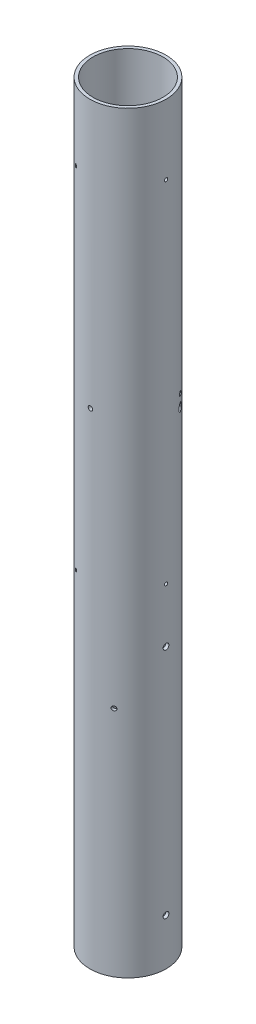
SolidWorks part; units mm, degrees
material "75 Degrees Custom Wound Fiberglass"
ref_plane "Front Plane" through (0, 0, 0) normal (0, 0, 1) x (1, 0, 0)
ref_plane "Top Plane" through (0, 0, 0) normal (0, 1, 0) x (1, 0, 0)
ref_plane "Right Plane" through (0, 0, 0) normal (1, 0, 0) x (0, 0, -1)
sketch "Sketch1" plane through (0, 0, 0) normal (0, 1, 0) x (1, 0, 0)
  circle A0 centre (0, 0) radius 38.227
  circle A1 centre (0, 0) radius 41.656
  dimension "D1" = 76.454
  dimension "D2" = 83.312
extrude "Boss-Extrude1" add sketch "Sketch1" along normal blind 822.5282
ref_axis "Axis1" through (0, -40.64, 0) along (0, 1, 0)
ref_plane "Plane1" through (-20.828, 0, 36.0752) normal (-0.5, 0, 0.866) x (0, -1, 0)
sketch "Sketch2" plane through (-20.828, 0, 36.0752) normal (-0.5, 0, 0.866) x (0, -1, 0)
  line L0 (40.64, 0) -> (-853.44, 0) construction
  line L1 (-822.5282, 38.227) -> (-822.5282, -38.227) construction
  line L2 (-822.5282, 38.227) -> (-822.5282, -38.227) construction
  circle A0 centre (-746.3282, 0) radius 1.778
  dimension "D1" = 76.2
  dimension "D2" = 3.556
extrude "S1A_Coupler" cut sketch "Sketch2" against normal up to next
pattern_circular "S1A_Coupler_Pattern" count 3 over 360 about axis through (0, -40.64, 0) along (0, 1, 0) of "S1A_Coupler"
ref_plane "Plane2" through (41.656, 0, 0) normal (1, 0, 0) x (0, 0, -1)
sketch "Sketch3" plane through (41.656, 0, 0) normal (1, 0, 0) x (0, 0, -1)
  line L0 (0, -40.64) -> (0, 853.44) construction
  circle A0 centre (0, 50.8) radius 3.175
  circle A1 centre (0, 304.8) radius 3.175
  dimension "D1" = 6.35
  dimension "D2" = 6.35
  dimension "D3" = 50.8
  dimension "D4" = 254
extrude "S1A_Rail_Guide" cut sketch "Sketch3" against normal up to next
ref_plane "Plane3" through (0, 530.4282, 0) normal (0, 1, 0) x (1, 0, 0)
ref_axis "Axis2" through (-19.4855, 746.3282, 33.7499) along (-0.5, 0, 0.866)
ref_plane "Plane4" through (-36.366, 0, -20.3159) normal (-0.873, 0, -0.4877) x (0, -1, 0)
sketch "Sketch4" plane through (-36.366, 0, -20.3159) normal (-0.873, 0, -0.4877) x (0, -1, 0)
  line L0 (-530.4282, 43.5864) -> (-530.4282, -43.5864) construction
  line L1 (40.64, 0) -> (-853.44, 0) construction
  circle A0 centre (-530.4282, 0) radius 2.3812
  dimension "D1" = 4.7625
extrude "S1A_Pressure" cut sketch "Sketch4" against normal up to next
pattern_circular "S1A_Pressure_Pattern" count 3 over 360 about axis through (0, -40.64, 0) along (0, 1, 0) of "S1A_Pressure"
ref_plane "Plane5" through (0, 511.3782, 0) normal (0, 1, 0) x (1, 0, 0)
ref_plane "Plane6" through (35.7771, 0, -21.3359) normal (0.8589, 0, -0.5122) x (0, -1, 0)
sketch "Sketch6" plane through (35.7771, 0, -21.3359) normal (0.8589, 0, -0.5122) x (0, -1, 0)
  line L0 (-518.9982, 0) -> (-516.4582, 0) construction
  line L1 (-518.9982, 3.175) -> (-516.4582, 3.175)
  line L2 (-518.9982, -3.175) -> (-516.4582, -3.175)
  line L3 (-822.5282, 0) -> (0, 0) construction
  line L4 (-822.5282, 41.656) -> (-822.5282, -41.656) construction
  arc A0 (-518.9982, 3.175) -> (-518.9982, -3.175) centre (-518.9982, 0) ccw
  arc A1 (-516.4582, -3.175) -> (-516.4582, 3.175) centre (-516.4582, 0) ccw
  point P1 (-517.7282, 0)
  dimension "D1" = 2.54
  dimension "D2" = 3.175
  dimension "D3" = 304.8
extrude "Switch_Slot" cut sketch "Sketch6" against normal up to next
ref_plane "Plane7" through (0, 254, 0) normal (0, 1, 0) x (1, 0, 0)
ref_plane "Plane8" through (20.828, 0, 36.0752) normal (0.5, 0, 0.866) x (0, -1, 0)
sketch "Sketch7" plane through (20.828, 0, 36.0752) normal (0.5, 0, 0.866) x (0, -1, 0)
  line L0 (-254, 43.5864) -> (-254, -43.5864) construction
  circle A0 centre (-254, 0) radius 2.3813
  dimension "D1" = 4.7625
extrude "S1A_Pressure_2" cut sketch "Sketch7" against normal up to next
pattern_circular "S1A_Pressure_2_Pattern" count 3 over 360 about axis through (0, -40.64, 0) along (0, 1, 0) of "S1A_Pressure_2"
sketch "Sketch8" plane through (-20.828, 0, 36.0752) normal (-0.5, 0, 0.866) x (0, -1, 0)
  circle A0 centre (-364.1217, 0) radius 1.7859
  dimension "D1" = 3.5719
  dimension "D2" = 364.1217
extrude "S1B_Propulsion_Bulkhead" cut sketch "Sketch8" against normal up to next
pattern_circular "S1B_Propulsion_Bulkhead_Pattern" count 3 over 360 about axis through (0, -40.64, 0) along (0, 1, 0) of "S1B_Propulsion_Bulkhead"
ref_plane "Plane9" through (0, 0, 41.656) normal (0, 0, 1) x (1, 0, 0)
ref_plane "Plane10" through (0, 0, 0) normal (0.866, 0, -0.5) x (0, 1, 0)
equation "\"D2@Sketch3\"=\"D1@Sketch3\""
equation "\"D2@Sketch1\"=\"D1@Sketch1\"+2*0.135"
